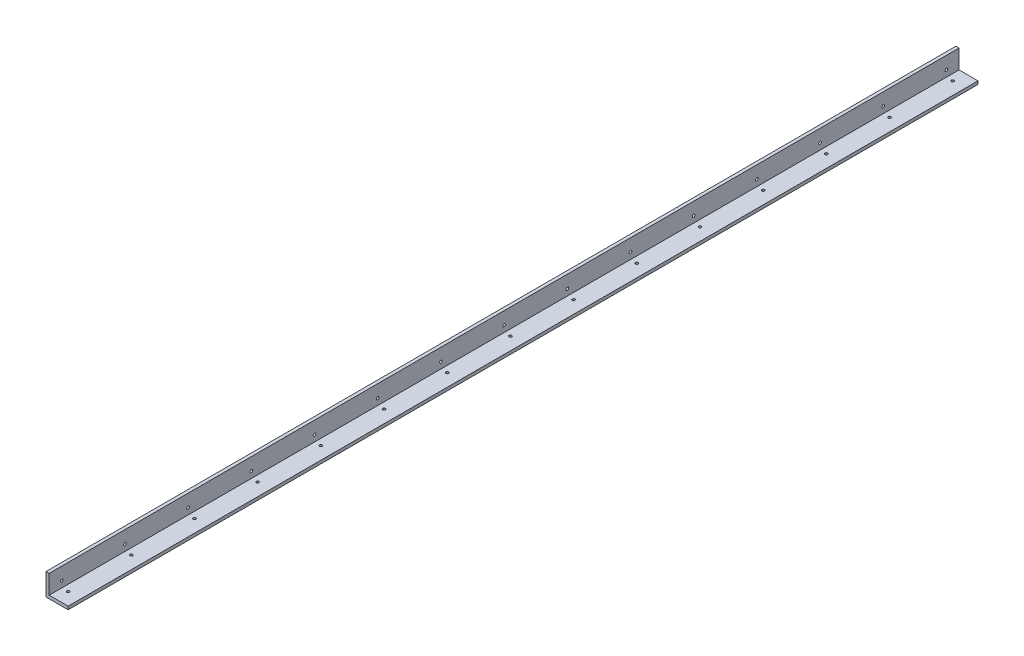
SolidWorks part; units mm, degrees
material "1060 Legierung"
ref_plane "Ebene vorne" through (0, 0, 0) normal (0, 0, 1) x (1, 0, 0)
ref_plane "Ebene oben" through (0, 0, 0) normal (0, 1, 0) x (1, 0, 0)
ref_plane "Ebene rechts" through (0, 0, 0) normal (1, 0, 0) x (0, 0, -1)
sketch "Skizze1" plane through (0, 0, 0) normal (0, 0, 1) x (1, 0, 0)
  line L0 (0, 0) -> (0, 35)
  line L1 (0, 35) -> (5, 35)
  line L2 (5, 35) -> (5, 5)
  line L3 (5, 5) -> (35, 5)
  line L4 (35, 5) -> (35, 0)
  line L5 (35, 0) -> (0, 0)
  dimension "D1" = 5
  dimension "D2" = 5
  dimension "D3" = 35
  dimension "D4" = 35
extrude "Aufsatz-Linear austragen1" add sketch "Skizze1" along normal blind 720 and the other way blind 720
hole_wizard "M5 Gewindebohrung1" positions "Skizze3" profile "Skizze2" tap size "M5" standard "Din"
sketch "Skizze3" plane through (0, 0, 0) normal (0, -1, 0) x (-1, 0, 0)
  line L1 (0, 720) -> (0, -720) construction
  line L2 (0, -720) -> (-35, -720) construction
  point P0 (-15, -700)
  dimension "D1" = 15
  dimension "D2" = 20
sketch "Skizze2" plane through (15, 0, 700) normal (1, 0, 0) x (0, 0, -1)
  line L0 (0, 0) -> (0, 15.2618)
  line L1 (0, 15.2618) -> (2.1, 14)
  line L2 (2.1, 14) -> (2.1, 0)
  line L5 (2.1, 0) -> (0, 0)
  line L10 (0, 15.2618) -> (-2.1, 14) construction
  line L11 (0, -6.35) -> (0, 107.95) construction
  dimension "Bohrerdurchmesser" = 4.2
  dimension "Bohrungstiefe" = 14
  dimension "Spitzenwinkel" = 118
cosmetic thread "Bohrungsgewinde1" parameters "D1"=5, "D2"=5
pattern_linear "Lineares Muster1" count 15 spacing 100 along (0, 0, -1) of "M5 Gewindebohrung1"
hole_wizard "M5 Gewindebohrung2" positions "Skizze5" profile "Skizze4" tap size "M5" standard "Din"
sketch "Skizze5" plane through (0, 0, 0) normal (-1, 0, 0) x (0, 0, 1)
  line L0 (-720, 0) -> (720, 0) construction
  line L4 (720, 35) -> (720, 0) construction
  point P0 (700, 15)
  dimension "D1" = 15
  dimension "D2" = 20
sketch "Skizze4" plane through (0, 15, 700) normal (0, 1, 0) x (0, 0, 1)
  line L0 (0, 0) -> (0, 15.2618)
  line L1 (0, 15.2618) -> (2.1, 14)
  line L2 (2.1, 14) -> (2.1, 0)
  line L5 (2.1, 0) -> (0, 0)
  line L10 (0, 15.2618) -> (-2.1, 14) construction
  line L11 (0, -6.35) -> (0, 107.95) construction
  dimension "Bohrerdurchmesser" = 4.2
  dimension "Bohrungstiefe" = 14
  dimension "Spitzenwinkel" = 118
cosmetic thread "Bohrungsgewinde2" parameters "D1"=5, "D2"=5
pattern_linear "Lineares Muster2" count 15 spacing 100 along (0, 0, -1) of "M5 Gewindebohrung2"
